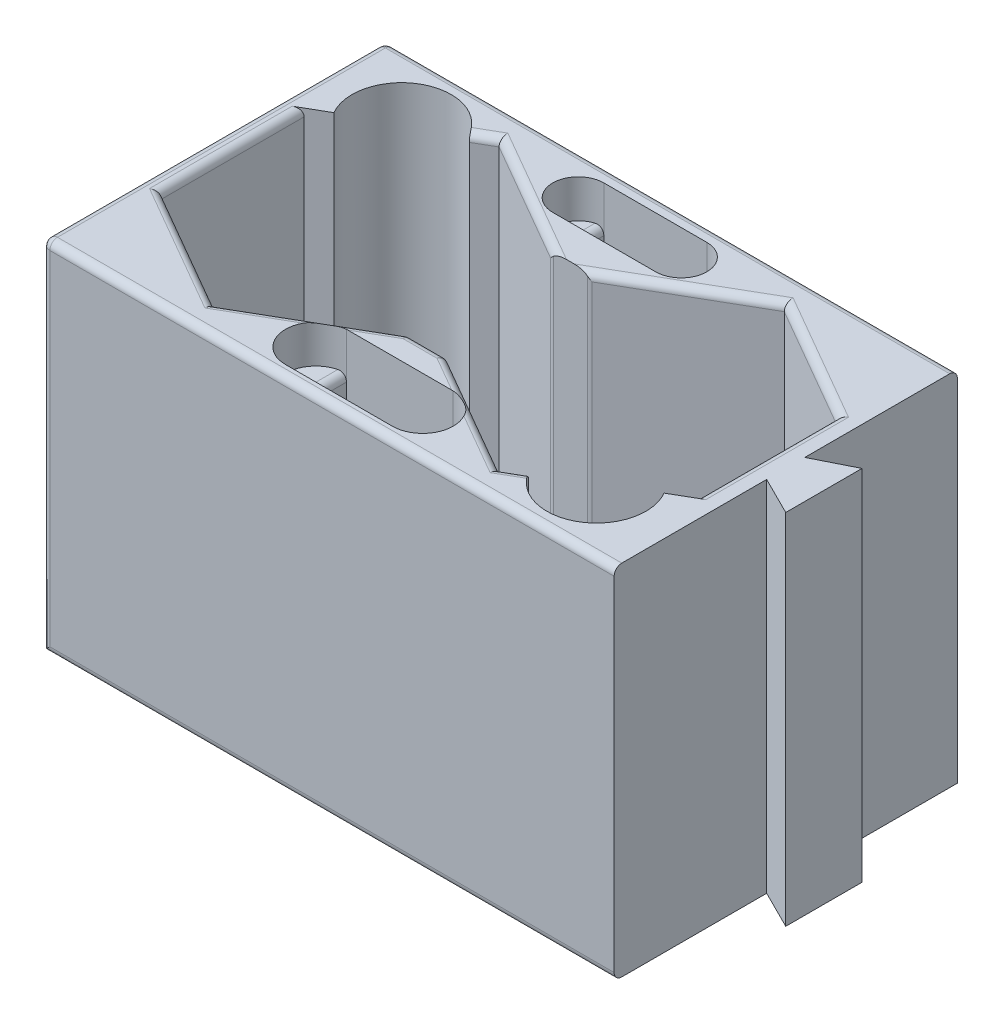
SolidWorks part; units mm, degrees
ref_plane "Front Plane" through (0, 0, 0) normal (0, 0, 1) x (1, 0, 0)
ref_plane "Top Plane" through (0, 0, 0) normal (0, 1, 0) x (1, 0, 0)
ref_plane "Right Plane" through (0, 0, 0) normal (1, 0, 0) x (0, 0, -1)
sketch "Sketch1" plane through (0, 0, 0) normal (0, 1, 0) x (1, 0, 0)
  line L0 (190.5, 63.5) -> (203.2, 69.85)
  line L1 (0, 0) -> (190.5, 0)
  line L2 (0, 0) -> (0, 114.3)
  line L3 (0, 114.3) -> (190.5, 114.3)
  line L4 (190.5, 0) -> (190.5, 50.8)
  line L5 (203.2, 69.85) -> (203.2, 44.45)
  line L6 (203.2, 44.45) -> (190.5, 50.8)
  line L7 (190.5, 63.5) -> (190.5, 114.3)
  dimension "D1" = 190.5
  dimension "D2" = 114.3
  dimension "D3" = 50.8
  dimension "D4" = 12.7
  dimension "D5" = 12.7
  dimension "D6" = 44.45
  dimension "D7" = 44.45
extrude "Boss-Extrude1" add sketch "Sketch1" along normal blind 119.38
sketch "Sketch2" plane through (0, 119.38, 0) normal (0, 1, 0) x (1, 0, 0)
  line L0 (0, 114.3) -> (0, 0) construction
  line L1 (47.498, 9.6364) -> (88.646, 33.3932)
  line L3 (88.646, 80.9068) -> (47.498, 104.6636)
  line L4 (47.498, 104.6636) -> (41.2221, 101.0402)
  line L5 (6.35, 80.9068) -> (6.35, 33.3932)
  line L6 (6.35, 33.3932) -> (12.6259, 29.7698)
  line L7 (142.494, 9.6364) -> (148.7699, 13.2598)
  line L8 (183.642, 33.3932) -> (183.642, 80.9068)
  line L9 (183.642, 80.9068) -> (177.3661, 84.5302)
  line L10 (142.494, 104.6636) -> (101.346, 80.9068)
  line L12 (101.346, 33.3932) -> (142.494, 9.6364)
  line L13 (0, 0) -> (190.5, 0) construction
  line L14 (88.646, 80.9068) -> (101.346, 80.9068)
  line L15 (101.346, 33.3932) -> (88.646, 33.3932)
  line L16 (148.7699, 101.0402) -> (142.494, 104.6636)
  line L17 (88.646, 57.15) -> (88.646, 80.9068) [skipped]
  line L18 (101.346, 57.15) -> (101.346, 33.3932) [skipped]
  line L19 (12.6259, 84.5302) -> (6.35, 80.9068)
  line L20 (41.2221, 13.2598) -> (47.498, 9.6364)
  line L21 (177.3661, 29.7698) -> (183.642, 33.3932)
  line L22 (148.7699, 101.0402) -> (177.3661, 84.5302)
  line L23 (12.6259, 29.7698) -> (41.2221, 13.2598)
  circle A0 centre (47.498, 57.15) radius 41.148 construction
  circle A1 centre (142.494, 57.15) radius 41.148 construction
  arc A3 (177.3661, 29.7698) -> (148.7699, 13.2598) centre (163.068, 21.5148) cw
  arc A4 (41.2221, 101.0402) -> (12.6259, 84.5302) centre (26.924, 92.7852) ccw
  dimension "D13" = 16.51
  dimension "D14" = 16.51
  dimension "D1" = 82.296
  dimension "D2" = 82.296
  dimension "D3" = 6.35
  dimension "D4" = 12.7
  dimension "D5" = 57.15
  dimension "D6" = 57.15
  dimension "D7" = 12.7
  dimension "D8" = 142.494
  dimension "D9" = 33.3932
  dimension "D10" = 88.646
  dimension "D17" = 7.2468
  dimension "D18" = 7.2468
extrude "Cut-Extrude1" cut sketch "Sketch2" against normal blind 115.57
sketch "Sketch3" plane through (0, 119.38, 0) normal (0, 1, 0) x (1, 0, 0)
  line L0 (190.5, 114.3) -> (0, 114.3) construction
  line L1 (77.851, 109.22) -> (112.141, 109.22)
  line L2 (77.851, 109.22) -> (77.851, 92.202)
  line L3 (77.851, 92.202) -> (112.141, 92.202)
  line L4 (112.141, 109.22) -> (112.141, 92.202)
  line L6 (101.346, 80.9068) -> (88.646, 80.9068) construction
  point P10 (94.996, 109.22)
  point P11 (94.996, 80.9068)
  dimension "D1" = 34.29
  dimension "D2" = 17.018
  dimension "D3" = 5.08
  dimension "D4" = 0
extrude "Cut-Extrude2" cut sketch "Sketch3" against normal blind 20.32
sketch "Sketch4" plane through (0, 119.38, 0) normal (0, 1, 0) x (1, 0, 0)
  line L0 (0, 0) -> (190.5, 0) construction
  line L1 (77.216, 24.13) -> (112.776, 24.13)
  line L2 (77.216, 24.13) -> (77.216, 3.81)
  line L3 (77.216, 3.81) -> (112.776, 3.81)
  line L4 (112.776, 24.13) -> (112.776, 3.81)
  line L5 (88.646, 33.3932) -> (101.346, 33.3932) construction
  point P6 (94.996, 24.13)
  point P9 (94.996, 33.3932)
  dimension "D1" = 35.56
  dimension "D2" = 20.32
  dimension "D3" = 3.81
  dimension "D4" = 0
extrude "Cut-Extrude3" cut sketch "Sketch4" against normal blind 35.56
sketch "Sketch5" plane through (0, 119.38, 0) normal (0, 1, 0) x (1, 0, 0)
  line L0 (112.141, 92.202) -> (112.141, 109.22) construction
  line L1 (77.851, 109.22) -> (77.851, 92.202) construction
  line L2 (112.776, 3.81) -> (112.776, 24.13) construction
  line L3 (77.216, 3.81) -> (112.776, 3.81) construction
  line L4 (77.216, 24.13) -> (77.216, 3.81) construction
  line L5 (77.851, 109.22) -> (77.851, 92.202)
  line L6 (112.141, 109.22) -> (112.141, 92.202)
  line L7 (112.776, 24.13) -> (112.776, 3.81)
  line L8 (77.216, 24.13) -> (77.216, 3.81)
  arc A0 (112.141, 109.22) -> (112.141, 92.202) centre (112.141, 100.711) cw
  arc A1 (77.851, 109.22) -> (77.851, 92.202) centre (77.851, 100.711) ccw
  arc A2 (112.776, 24.13) -> (112.776, 3.81) centre (112.776, 13.97) cw
  arc A3 (77.216, 24.13) -> (77.216, 3.81) centre (77.216, 13.97) ccw
extrude "Cut-Extrude4" cut sketch "Sketch5" against normal blind 12.7
fillet "Fillet1" radius 2.54 6 edges at (95.25, 119.38, -114.3) (95.25, 119.38, 0) (95.25, 0, 0) (0, 119.38, -57.15) (0, 59.69, -114.3) (0, 59.69, 0)
fillet "Fillet2" radius 2.54 19 edges at (112.141, 106.68, -100.711) (77.851, 106.68, -100.711) (112.776, 106.68, -13.97) (77.216, 106.68, -13.97) (121.92, 119.38, -92.7852) (163.068, 119.38, -92.7852) (183.642, 119.38, -57.15) (145.632, 119.38, -11.4481) (121.92, 119.38, -21.5148) (94.996, 119.38, -33.3932) (68.072, 119.38, -21.5148) (26.924, 119.38, -21.5148) (6.35, 119.38, -57.15) (44.36, 119.38, -102.8519) (68.072, 119.38, -92.7852) (88.646, 61.595, -33.3932) (101.346, 61.595, -33.3932) (88.646, 61.595, -80.9068) (101.346, 61.595, -80.9068)
